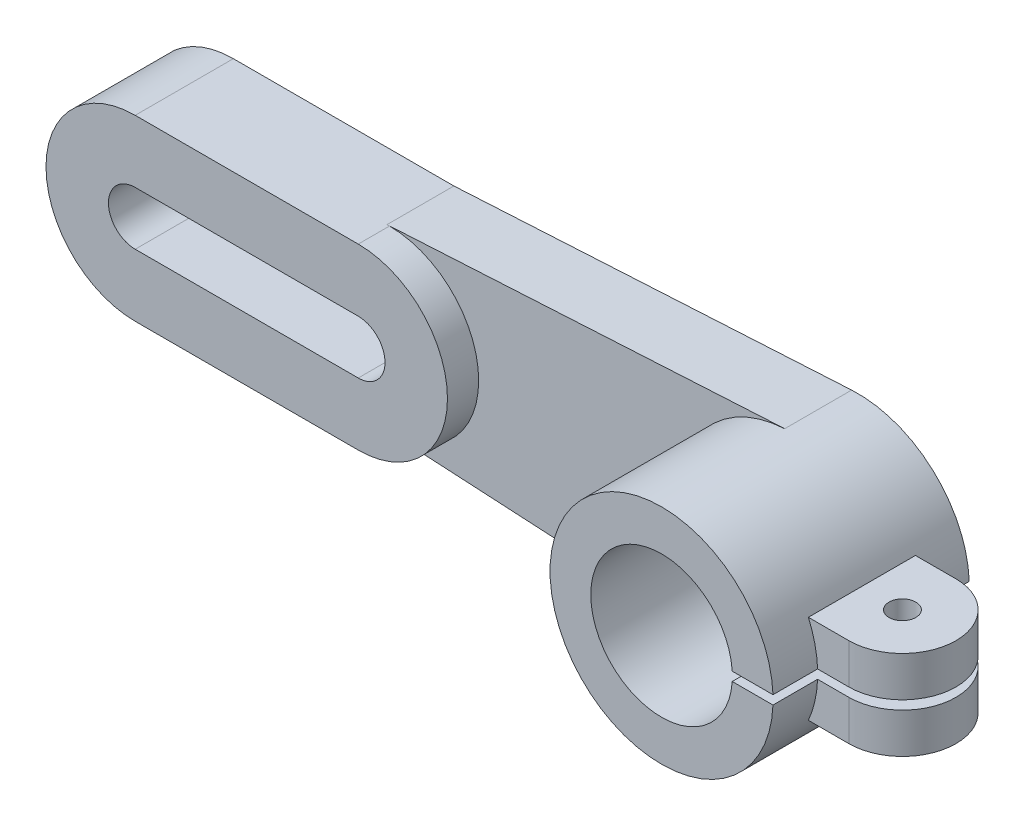
SolidWorks part; units mm, degrees
ref_plane "Front Plane" through (0, 0, 0) normal (0, 0, 1) x (1, 0, 0)
ref_plane "Top Plane" through (0, 0, 0) normal (0, 1, 0) x (1, 0, 0)
ref_plane "Right Plane" through (0, 0, 0) normal (1, 0, 0) x (0, 0, -1)
sketch "Sketch1" plane through (0, 0, 0) normal (0, 0, 1) x (1, 0, 0)
  line L0 (18.8556, 0) -> (-24551.9163, 0) construction
  line L1 (0, 0) -> (0, -24551.9163) construction
  line L2 (-140, 0) -> (-90, 0) construction
  line L3 (-140, 6) -> (-90, 6)
  line L4 (-140, -6) -> (-90, -6)
  line L5 (-140, 0) -> (-90, 0) construction
  line L6 (-140, 20) -> (-90, 20)
  line L7 (-140, -20) -> (-90, -20)
  line L8 (15.836, 1) -> (24.98, 1)
  line L9 (15.836, -1) -> (24.98, -1)
  line L10 (22.9129, -10) -> (44, -10)
  line L13 (22.9129, 10) -> (44, 10)
  line L14 (44, 1) -> (44, 10)
  line L15 (44, -1) -> (44, -10)
  line L17 (-91.1111, 19.9691) -> (-1.3889, 24.9614)
  line L18 (-91.1111, -19.9691) -> (-1.3889, -24.9614)
  line L19 (24.98, 1) -> (44, 1)
  line L20 (24.98, -1) -> (44, -1)
  arc A0 (15.836, 1) -> (15.836, -1) centre (0, 0) ccw
  arc A1 (24.98, 1) -> (24.98, -1) centre (0, 0) ccw
  arc A2 (-140, 6) -> (-140, -6) centre (-140, 0) ccw
  arc A3 (-90, -6) -> (-90, 6) centre (-90, 0) ccw
  arc A4 (-140, 20) -> (-140, -20) centre (-140, 0) ccw
  arc A5 (-90, -20) -> (-90, 20) centre (-90, 0) ccw
  point P10 (-115, 0)
  point P15 (-115, 0)
  dimension "D1" = 50
  dimension "D2" = 31.735
  dimension "D3" = 12
  dimension "D4" = 50
  dimension "D5" = 40
  dimension "D6" = 140
  dimension "D7" = 2
  dimension "D8" = 20
  dimension "D9" = 44
extrude "Boss-Extrude1" add sketch "Sketch1" against normal blind 44 contours L8 A1 L9 A0 region at (12.7359, 20.6869, 0)
extrude "Boss-Extrude2" add sketch "Sketch1<3>" against normal blind 24 from offset 10 contours A1 L19 L14 L13 | A1 L10 L15 L20 region at (34.1112, 5.5779, 0) region at (34.1112, -5.5779, 0) offset against normal yes
sketch "Sketch1<3>" plane through (0, 0, 0) normal (0, 0, 1) x (1, 0, 0) same geometry as "Sketch1"
extrude "Boss-Extrude3" add sketch "Sketch1<4>" against normal blind 22 from offset 22 separate body contours L7 A5 L6 A4 A3 L4 A2 L3 region at (-115.278, 19.0151, 0) offset against normal yes
sketch "Sketch1<4>" plane through (0, 0, 0) normal (0, 0, 1) x (1, 0, 0) same geometry as "Sketch1"
extrude "Boss-Extrude4" add sketch "Sketch1<5>" against normal blind 15 from offset 29 contours A5 L7 L18 A1 L17 L6 region at (-46.6609, 0, 0) offset against normal yes
sketch "Sketch1<5>" plane through (0, 0, 0) normal (0, 0, 1) x (1, 0, 0) same geometry as "Sketch1"
fillet "Fillet1" 2 edges at (44, 5.5, -10) (44, 5.5, -34) type full round first side face at (34.078, 5.5241, -10) second side face at (34.078, 5.5241, -34) middle face at (44, 5.5, -22)
fillet "Fillet2" 2 edges at (44, -5.5, -10) (44, -5.5, -34) type full round first side face at (34.078, -5.5241, -10) second side face at (34.078, -5.5241, -34) middle face at (44, -5.5, -22)
hole_wizard "Ø6.0mm Dowel Hole1" positions "3DSketch2" profile "Sketch2" hole size "Ø6.0" standard "ANSI Metric" end condition through all
sketch3d "3DSketch2"
  line L0 (32, 1, -22) -> (32, 10, -22) construction
  point P0 (32, 10, -22)
sketch "Sketch2" plane through (32, 10, -22) normal (1, 0, 0) x (0, 0, 1)
  line L0 (0, 0) -> (0, 35)
  line L1 (0, 35) -> (3, 35)
  line L2 (3, 35) -> (3, 0)
  line L5 (3, 0) -> (0, 0)
  line L11 (0, -6.35) -> (0, 107.95) construction
  dimension "Thru Hole Dia." = 6
  dimension "Thru Hole Depth" = 35
